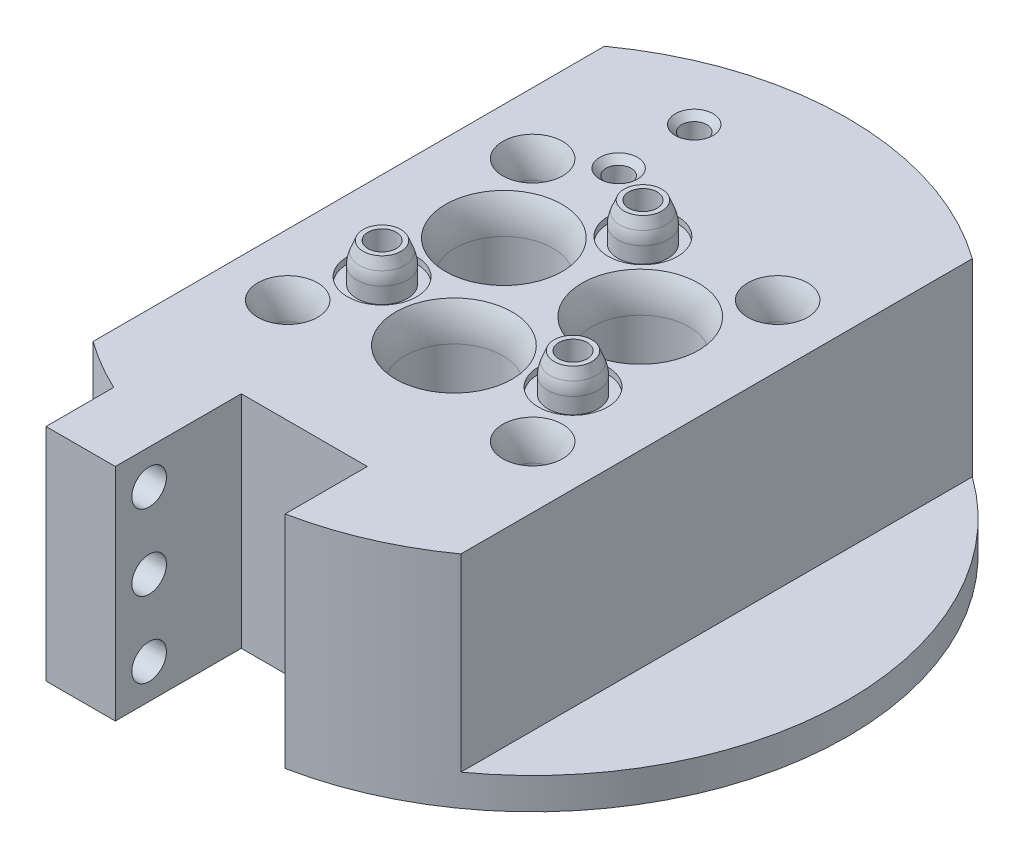
SolidWorks part; units mm, degrees
note: The reader was unsure of these and kept them because the rebuilt part matched: shared geometry of "Çizim1<3>", "Çizim4<3>", "Çizim3<5>", "Çizim3<3>".
ref_plane "Ön Düzlem" through (0, 0, 0) normal (0, 0, 1) x (1, 0, 0)
ref_plane "Üst Düzlem" through (0, 0, 0) normal (0, 1, 0) x (1, 0, 0)
ref_plane "Sağ Düzlem" through (0, 0, 0) normal (1, 0, 0) x (0, 0, -1)
sketch "Çizim1" plane through (0, 0, 0) normal (0, 1, 0) x (1, 0, 0)
  line L0 (0, 0) -> (0, 50) construction
  line L1 (-29.199, 40.5884) -> (-29.199, -40.5884)
  line L2 (-47.199, 16.5) -> (-29.199, 16.5)
  line L3 (-47.199, 16.5) -> (-47.199, -16.5)
  line L4 (-47.199, -16.5) -> (-29.199, -16.5)
  line L5 (-29.199, 16.5) -> (-29.199, -16.5)
  line L6 (29.199, 40.5884) -> (29.199, -40.5884)
  line L7 (47.199, -16.5) -> (29.199, -16.5)
  line L8 (29.199, 16.5) -> (29.199, -16.5)
  line L9 (47.199, 16.5) -> (29.199, 16.5)
  line L10 (47.199, 16.5) -> (47.199, -16.5)
  circle A0 centre (0, 0) radius 50
  point P8 (-29.199, 0)
  dimension "D1" = 100
  dimension "D2" = 18
  dimension "D3" = 33
extrude "base" add sketch "Çizim1" against normal blind 5
extrude "Yükseklik-Ekstrüzyon2" add sketch "Çizim1<3>" along normal blind 30
sketch "Çizim1<3>" plane through (0, 0, 0) normal (0, 1, 0) x (1, 0, 0) same geometry as "Çizim1"
sketch "Çizim2" plane through (0, 30, 0) normal (0, 1, 0) x (1, 0, 0)
  line L0 (-11.3, 30.9428) -> (29.199, 30.9428) construction
  line L2 (29.199, 40.5884) -> (29.199, -40.5884) construction
  circle A1 centre (-11.3, 36.9428) radius 2
  circle A2 centre (-11.3, 24.9428) radius 2
  dimension "D1" = 4
  dimension "D2" = 6
extrude "banana slotu" cut sketch "Çizim2" against normal through all
chamfer "Pah1" distance 1 angle 45 2 edges at (-11.3, 30, -34.9428) (-11.3, 30, -26.9428)
sketch "Çizim3" plane through (0, 30, 0) normal (0, 1, 0) x (1, 0, 0)
  line L0 (-19.4454, -19.4454) -> (0, 0) construction
  line L1 (0, 0) -> (-35, 0) construction
  circle A0 centre (0, 0) radius 35 construction
  circle A1 centre (0, 0) radius 35 construction
  circle A2 centre (0, -12.5) radius 2.75
  circle A3 centre (-19.4454, -19.4454) radius 1.75
  circle A4 centre (0, 17.5) radius 2.25
  point P18 (0, 0)
  point P23 (0, 0)
  dimension "D1" = 70
  dimension "D2" = 70
  dimension "D5" = 5.5
  dimension "D6" = 4.5
  dimension "D7" = 3.5
  dimension "D3" = 12.5
  dimension "D4" = 17.5
  dimension "D8" = 27.5
  dimension "D9" = 45
sketch "Çizim4" plane through (0, -5, 0) normal (0, -1, 0) x (1, 0, 0)
  line L12 (9.75, 36) -> (-10.25, 36)
  line L13 (-21.25, 32.3796) -> (-21.25, 56)
  line L14 (-10.25, 36) -> (-10.25, 56)
  line L15 (-21.25, 56) -> (-10.25, 56)
  line L16 (9.75, 36) -> (9.75, 49.0402)
  circle A3 centre (0, 0) radius 35
  arc A10 (14.2812, 31.9538) -> (-24.3056, 25.1841) centre (0, 0) ccw
  arc A11 (9.75, 36) -> (14.2812, 31.9538) centre (18.3615, 41.0835) ccw
  arc A12 (-24.3056, 25.1841) -> (-21.25, 32.3796) centre (-31.25, 32.3796) ccw
  circle A13 centre (0, 0) radius 50 construction
  arc A14 (-10.25, 48.9381) -> (9.75, 49.0402) centre (0, 0) cw
  circle A19 centre (0, 0) radius 35 construction
  point P9 (0, 0)
  point P10 (9.6136, 49.0671)
  point P42 (0, 0)
  circle M11 centre (0, 0) radius 50
  dimension "D2" = 11
  dimension "D7" = 70
  dimension "D1" = 10
  dimension "D3" = 20
  dimension "D4" = 20
  dimension "D5" = 9.75
  dimension "D6" = 36
extrude "Yükseklik-Ekstrüzyon3" add sketch "Çizim4" against normal blind 35
extrude "sigma slot" cut sketch "Çizim4<3>" against normal through all contours L12 L16 L14 M11
sketch "Çizim4<3>" plane through (0, -5, 0) normal (0, -1, 0) x (1, 0, 0) same geometry as "Çizim4"
extrude "delikler" cut sketch "Çizim3" against normal through all contours A4
extrude "Kes-Ekstrüzyon8" cut sketch "Çizim3<5>" against normal through all contours A2
sketch "Çizim3<5>" plane through (0, 30, 0) normal (0, 1, 0) x (1, 0, 0) same geometry as "Çizim3"
sketch "Çizim5" plane through (0, 30, 0) normal (0, 1, 0) x (1, 0, 0)
  circle A0 centre (0, 17.5) radius 5.5
  dimension "D1" = 11
extrude "Kes-Ekstrüzyon3" cut sketch "Çizim5" against normal blind 1
extrude "Kes-Ekstrüzyon6" cut sketch "Çizim3<3>" against normal through all contours A3
sketch "Çizim3<3>" plane through (0, 30, 0) normal (0, 1, 0) x (1, 0, 0) same geometry as "Çizim3"
sketch "Çizim6" plane through (0, 30, 0) normal (0, 1, 0) x (1, 0, 0)
  circle A0 centre (0, -12.5) radius 7.75
  circle A1 centre (0, -12.5) radius 2.75 construction
  dimension "D1" = 15.5
extrude "Kes-Ekstrüzyon4" cut sketch "Çizim6" against normal blind 16
sketch "Çizim7" plane through (0, 30, 0) normal (0, 1, 0) x (1, 0, 0)
  circle A0 centre (-19.4454, -19.4454) radius 3.25
  circle A1 centre (-19.4454, -19.4454) radius 1.75 construction
  point P3 (0, 0)
  dimension "D1" = 6.5
extrude "Kes-Ekstrüzyon5" cut sketch "Çizim7" against normal blind 10
sketch "Çizim8" plane through (0, 29, 0) normal (0, 1, 0) x (1, 0, 0)
  circle A0 centre (0, 17.5) radius 4
  circle A1 centre (0, 17.5) radius 2.25
  circle A2 centre (0, 17.5) radius 2.25 construction
  circle M3 centre (0, 17.5) radius 2.25
  dimension "D1" = 8
extrude "Yükseklik-Ekstrüzyon4" add sketch "Çizim8" along normal blind 6 contours A0 M3
chamfer "Pah2" distance 2.5 distance2 1 1 edges at (0, 35, -13.5)
fillet "Radyus1" radius 5 1 edges at (0, 32.5, -13.5)
pattern_circular "Dairesel Kaplama10" count 3 over 360 about axis through (0, 0, 0) along (0, 1, 0) of "Kes-Ekstrüzyon4", "Kes-Ekstrüzyon8"
pattern_circular "Dairesel Kaplama8" count 3 over 360 about axis through (0, 0, 0) along (0, 1, 0) of "delikler", "Pah2", "Radyus1", "Yükseklik-Ekstrüzyon4", "Kes-Ekstrüzyon3"
pattern_circular "Dairesel Kaplama11" count 4 over 360 about axis through (0, 0, 0) along (0, 1, 0) of "Kes-Ekstrüzyon6", "Kes-Ekstrüzyon5"
chamfer "Pah4" distance 1.5 angle 45 7 edges at (22.6954, 30, 19.4454) (-19.4454, 30, 22.6954) (0, 30, 20.25) (19.4454, 30, -22.6954) (17.537, 30, -10.125) (-17.537, 30, -10.125) (-22.6954, 30, -19.4454)
fillet "Radyus3" radius 10 7 edges at (19.4454, 28.5, 22.6954) (19.4454, 28.5, -16.1954) (10.8253, 28.5, 1.5) (0, 28.5, 20.25) (-19.4454, 28.5, 22.6954) (-10.8253, 28.5, 1.5) (-19.4454, 28.5, -16.1954)
sketch "Çizim9" plane through (-21.25, 0, 0) normal (-1, 0, 0) x (0, 0, 1)
  line L0 (56, 12.5) -> (45.2597, 12.5) construction
  line L1 (56, 30) -> (56, -5) construction
  line L2 (45.2597, 30) -> (45.2597, -5) construction
  line L3 (50.6298, 24.5) -> (50.6298, 12.5) construction
  circle A0 centre (50.6298, 24.5) radius 2.75
  circle A1 centre (50.6298, 12.5) radius 2.75
  circle A2 centre (50.6298, 0.5) radius 2.75
  point P8 (49.1681, 10.59)
  point P9 (0, 0)
  dimension "D1" = 5.5
  dimension "D3" = 12
  dimension "D2" = 3
extrude "Kes-Ekstrüzyon9" cut sketch "Çizim9" against normal up to next
